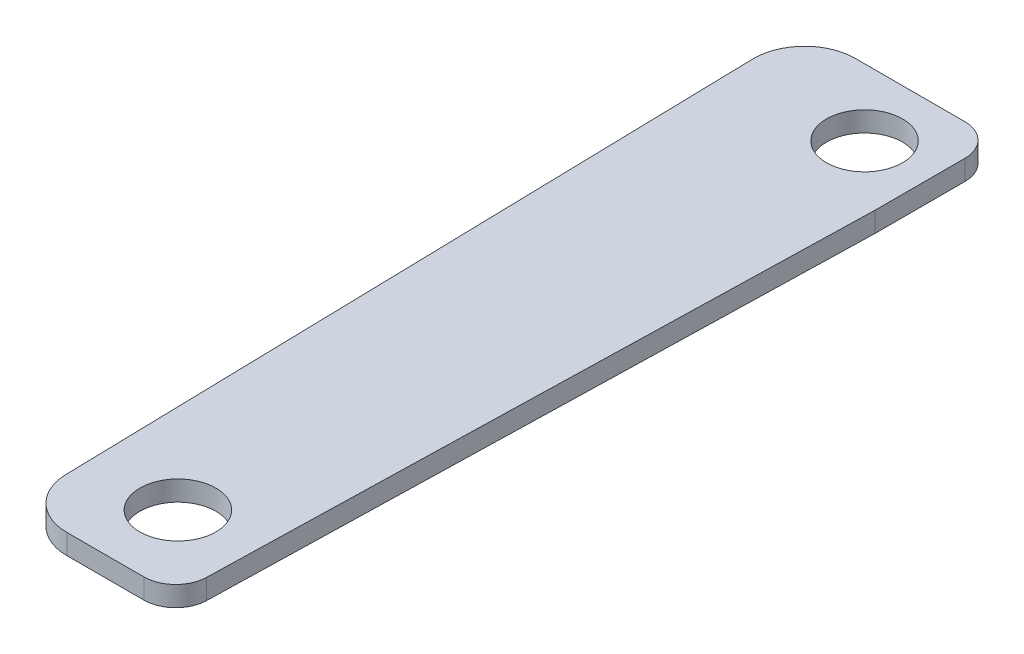
SolidWorks part; units mm, degrees
ref_plane "Front" through (0, 0, 0) normal (0, 0, 1) x (1, 0, 0)
ref_plane "Top" through (0, 0, 0) normal (0, 1, 0) x (1, 0, 0)
ref_plane "Right" through (0, 0, 0) normal (1, 0, 0) x (0, 0, -1)
sketch "Sketch1" plane through (0, 0, 0) normal (0, 1, 0) x (1, 0, 0)
  line L1 (0, 0) -> (38.1, 0)
  line L2 (0, 0) -> (0, 127)
  line L3 (0, 127) -> (38.1, 127)
  line L4 (38.1, 0) -> (38.1, 127)
  dimension "D1" = 38.1
  dimension "D2" = 127
extrude "Boss-Extrude1" add sketch "Sketch1" along normal blind 3.175
sketch "Sketch3" plane through (0, 3.175, 0) normal (0, 1, 0) x (1, 0, 0)
  circle A0 centre (27.7881, 116.4638) radius 6
  circle A1 centre (24.0611, 11.824) radius 6
extrude "Cut-Extrude1" cut sketch "Sketch3" against normal blind 10
sketch "Sketch4" plane through (0, 3.175, 0) normal (0, 1, 0) x (1, 0, 0)
  line L0 (0, 127) -> (7.5922, 127)
  line L1 (38.1, 127) -> (0, 127) construction
  line L2 (7.5922, 127) -> (10.5594, 0)
  line L3 (0, 0) -> (38.1, 0) construction
  line L4 (10.5594, 0) -> (33.2799, 0)
  line L5 (33.2799, 0) -> (35.4124, 0)
  line L6 (35.4124, 0) -> (38.1, 107.8224)
  line L7 (38.1, 0) -> (38.1, 127) construction
  line L8 (38.1, 107.8224) -> (63.3213, 4.6264)
  line L9 (63.3213, 4.6264) -> (13.3195, -14.6846)
  line L10 (13.3195, -14.6846) -> (-13.2582, -5.0291)
  line L11 (-13.2582, -5.0291) -> (0, 127)
extrude "Cut-Extrude2" cut sketch "Sketch4" against normal blind 10
fillet "Fillet2" radius 5 2 edges at (38.1, 1.5875, -127) (35.4124, 1.5875, 0)
fillet "Fillet3" radius 8 2 edges at (10.5594, 1.5875, 0) (7.5922, 1.5875, -127)
